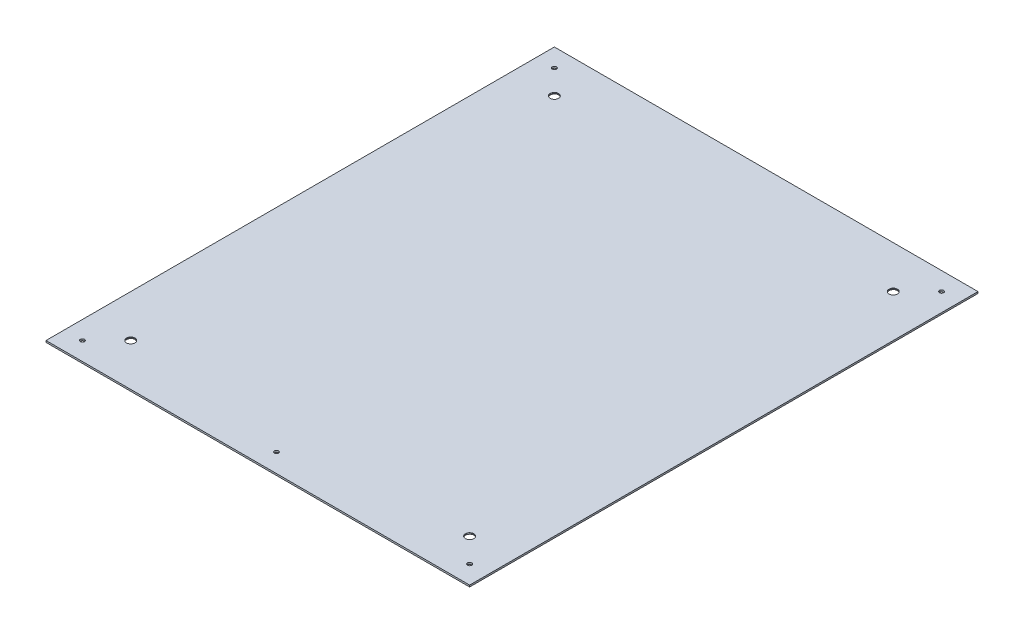
SolidWorks part; units mm, degrees
ref_plane "Front Plane" through (0, 0, 0) normal (0, 0, 1) x (1, 0, 0)
ref_plane "Top Plane" through (0, 0, 0) normal (0, 1, 0) x (1, 0, 0)
ref_plane "Right Plane" through (0, 0, 0) normal (1, 0, 0) x (0, 0, -1)
sketch "Sketch1" plane through (0, 0, 0) normal (0, 1, 0) x (1, 0, 0)
  line L1 (-250, 300) -> (250, 300)
  line L2 (-250, 300) -> (-250, -300)
  line L3 (-250, -300) -> (250, -300)
  line L4 (250, 300) -> (250, -300)
  circle A0 centre (-228.5, 278.5) radius 2.5
  circle A1 centre (228.5, 278.5) radius 2.5
  circle A2 centre (228.5, -278.5) radius 2.5
  circle A3 centre (-228.5, -278.5) radius 2.5
  point P0 (0, 0)
  dimension "D3" = 5
  dimension "D1" = 500
  dimension "D2" = 600
  dimension "D4" = 21.5
  dimension "D5" = 578.5
  dimension "D6" = 21.5
  dimension "D7" = 21.5
base flange "Base-Flange1" sketch "Sketch1" thickness 2 reverse thickness direction no parameters "D1"=6.35
sketch "Sketch3" plane through (0, 0, 0) normal (0, 1, 0) x (1, 0, 0)
  line L0 (250, 300) -> (-250, 300) construction
  line L1 (-250, 300) -> (-250, -300) construction
  line L2 (0, 0) -> (0, 300) construction
  line L3 (-250, 0) -> (250, 0) construction
  line L4 (250, -300) -> (250, 300) construction
  circle A0 centre (-200, 250) radius 5
  circle A1 centre (200, 250) radius 5
  circle A2 centre (-200, -250) radius 5
  circle A3 centre (200, -250) radius 5
  dimension "D1" = 10
  dimension "D2" = 50
  dimension "D3" = 50
extrude "Cut-Extrude2" cut sketch "Sketch3" against normal through all normal cut yes
thread "Thread1" pitch 1.25 method cut profile "Thread Profile1" start angle 0, offset 0, length 0, pitch 1.25, diameter 10
ref_plane "Plane1" through (-205, 0, -250) normal (0, 0, 1) x (-1, 0, 0)
sketch "Thread Profile1" plane through (-205, 0, -250) normal (0, 0, 1) x (-1, 0, 0)
  line L0 (0, 0) -> (0, 1.25) construction
  line L1 (0, 0) -> (0.6766, 0.3906)
  line L2 (0.6766, 0.3906) -> (0.6766, 0.5469)
  line L3 (0.6766, 0.5469) -> (0, 0.9375)
  line L4 (0.6766, 0.4687) -> (0, 0.4687) construction
  line L11 (0, 0) -> (0, 0.9375)
  point P2 (0, 0)
  dimension "Pitch" = 1.25
  dimension "Profile_Angle" = 60
  dimension "Profile_Land" = 0.1562
  dimension "Profile_Height" = 0.6766
thread "Thread2" pitch 1.25 method cut profile "Thread Profile2" start angle 0, offset 0, length 0, pitch 1.25, diameter 10
ref_plane "Plane2" through (-205, 0, 250) normal (0, 0, 1) x (-1, 0, 0)
sketch "Thread Profile2" plane through (-205, 0, 250) normal (0, 0, 1) x (-1, 0, 0)
  line L0 (0, 0) -> (0, 1.25) construction
  line L1 (0, 0) -> (0.6766, 0.3906)
  line L2 (0.6766, 0.3906) -> (0.6766, 0.5469)
  line L3 (0.6766, 0.5469) -> (0, 0.9375)
  line L4 (0.6766, 0.4687) -> (0, 0.4687) construction
  line L11 (0, 0) -> (0, 0.9375)
  point P2 (0, 0)
  dimension "Pitch" = 1.25
  dimension "Profile_Angle" = 60
  dimension "Profile_Land" = 0.1562
  dimension "Profile_Height" = 0.6766
thread "Thread3" pitch 1.25 method cut profile "Thread Profile3" start angle 0, offset 0, length 0, pitch 1.25, diameter 10
ref_plane "Plane3" through (195, 0, -250) normal (0, 0, 1) x (-1, 0, 0)
sketch "Thread Profile3" plane through (195, 0, -250) normal (0, 0, 1) x (-1, 0, 0)
  line L0 (0, 0) -> (0, 1.25) construction
  line L1 (0, 0) -> (0.6766, 0.3906)
  line L2 (0.6766, 0.3906) -> (0.6766, 0.5469)
  line L3 (0.6766, 0.5469) -> (0, 0.9375)
  line L4 (0.6766, 0.4687) -> (0, 0.4687) construction
  line L11 (0, 0) -> (0, 0.9375)
  point P2 (0, 0)
  dimension "Pitch" = 1.25
  dimension "Profile_Angle" = 60
  dimension "Profile_Land" = 0.1562
  dimension "Profile_Height" = 0.6766
thread "Thread4" pitch 1.25 method cut profile "Thread Profile4" start angle 0, offset 0, length 0, pitch 1.25, diameter 10
ref_plane "Plane4" through (195, 0, 250) normal (0, 0, 1) x (-1, 0, 0)
sketch "Thread Profile4" plane through (195, 0, 250) normal (0, 0, 1) x (-1, 0, 0)
  line L0 (0, 0) -> (0, 1.25) construction
  line L1 (0, 0) -> (0.6766, 0.3906)
  line L2 (0.6766, 0.3906) -> (0.6766, 0.5469)
  line L3 (0.6766, 0.5469) -> (0, 0.9375)
  line L4 (0.6766, 0.4687) -> (0, 0.4687) construction
  line L11 (0, 0) -> (0, 0.9375)
  point P2 (0, 0)
  dimension "Pitch" = 1.25
  dimension "Profile_Angle" = 60
  dimension "Profile_Land" = 0.1562
  dimension "Profile_Height" = 0.6766
sketch "Sketch6" plane through (0, 0, 0) normal (0, 1, 0) x (1, 0, 0)
  line L2 (-250, -300) -> (250, -300) construction
  circle A2 centre (0, -278) radius 2.463
  dimension "D1" = 22
extrude "Cut-Extrude4" cut sketch "Sketch6" against normal blind 10 normal cut yes
sketch "Bend-Lines1"
sketch "Bounding-Box1" plane through (0, 0, 0) normal (0, 1, 0) x (1, 0, 0)
sheet metal parameters "Sheet-Metal1" thickness 2 parameters "D1"=6.35
flat pattern "Flat-Pattern1" [suppressed]
sketch "Bend-Lines2" plane through (0, 0, 0) normal (0, 1, 0) x (1, 0, 0)
sketch "Bounding-Box2" [suppressed] plane through (0, 0, 0) normal (0, 1, 0) x (1, 0, 0)
sheet metal parameters "Sheet-Metal3" thickness 2 parameters "D1"=6.35
flat pattern "Flat-Pattern1"
sketch "Bend-Lines2" plane through (0, 0, 0) normal (0, 1, 0) x (1, 0, 0)
sketch "Bounding-Box2" [suppressed] plane through (0, 0, 0) normal (0, 1, 0) x (1, 0, 0)
sheet metal parameters "Sheet-Metal4" thickness 2 parameters "D1"=6.35
flat pattern "Flat-Pattern1"
sketch "Bend-Lines2" plane through (0, 0, 0) normal (0, 1, 0) x (1, 0, 0)
sketch "Bounding-Box2" [suppressed] plane through (0, 0, 0) normal (0, 1, 0) x (1, 0, 0)
sheet metal parameters "Sheet-Metal5" thickness 2 parameters "D1"=6.35
flat pattern "Flat-Pattern1"
sketch "Bend-Lines2" plane through (0, 0, 0) normal (0, 1, 0) x (1, 0, 0)
sketch "Bounding-Box2" [suppressed] plane through (0, 0, 0) normal (0, 1, 0) x (1, 0, 0)
sheet metal parameters "Sheet-Metal6" thickness 2 parameters "D1"=6.35
flat pattern "Flat-Pattern1"
sketch "Bend-Lines2" plane through (0, 0, 0) normal (0, 1, 0) x (1, 0, 0)
sketch "Bounding-Box2" [suppressed] plane through (0, 0, 0) normal (0, 1, 0) x (1, 0, 0)
sheet metal parameters "Sheet-Metal7" thickness 2 parameters "D1"=6.35
flat pattern "Flat-Pattern1"
sketch "Bend-Lines2" plane through (0, 0, 0) normal (0, 1, 0) x (1, 0, 0)
sketch "Bounding-Box2" [suppressed] plane through (0, 0, 0) normal (0, 1, 0) x (1, 0, 0)
sheet metal parameters "Sheet-Metal9" thickness 2 parameters "D1"=6.35
flat pattern "Flat-Pattern1" [suppressed]
sketch "Bend-Lines2" plane through (0, 0, 0) normal (0, 1, 0) x (1, 0, 0)
sketch "Bounding-Box2" [suppressed] plane through (0, 0, 0) normal (0, 1, 0) x (1, 0, 0)
